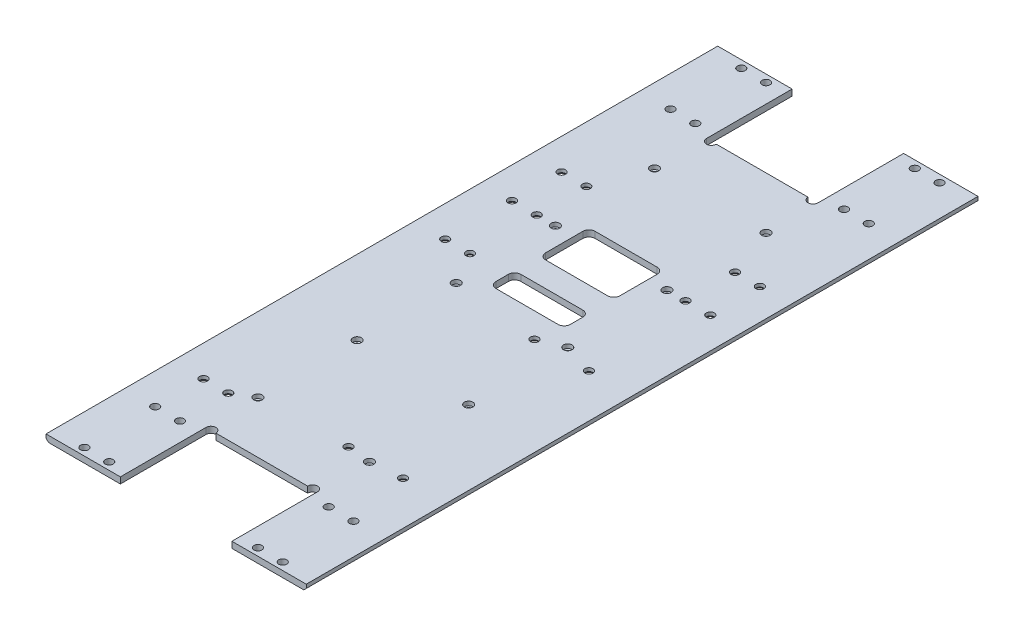
SolidWorks part; units mm, degrees
ref_plane "前视基准面" through (0, 0, 0) normal (0, 0, 1) x (1, 0, 0)
ref_plane "上视基准面" through (0, 0, 0) normal (0, 1, 0) x (1, 0, 0)
ref_plane "右视基准面" through (0, 0, 0) normal (1, 0, 0) x (0, 0, -1)
sketch "草图1" plane through (0, 0, 0) normal (0, 1, 0) x (1, 0, 0)
  line L6 (-52.5, -135.5) -> (52.5, -135.5)
  line L7 (52.5, -135.5) -> (52.5, 135.5)
  line L8 (-52.5, 135.5) -> (52.5, 135.5)
  line L9 (-52.5, -135.5) -> (-52.5, 135.5)
  point P8 (-50, 0)
extrude "凸台-拉伸1" add sketch "草图1" along normal blind 2.5
sketch "草图2" plane through (0, 2.5, 0) normal (0, 1, 0) x (1, 0, 0)
  circle A20 centre (13, -3.95) radius 1.6
  circle A21 centre (35, -3.95) radius 1.6
  circle A24 centre (35, -78.95) radius 1.6
  circle A25 centre (13, -78.95) radius 1.6
extrude "切除-拉伸1" cut sketch "草图2" against normal blind 10
chamfer "倒角4" distance 1 angle 45 2 edges at (52.5, 0, 0) (-52.5, 0, 0)
sketch "草图3" plane through (0, 0, 0) normal (0, -1, 0) x (1, 0, 0)
  line L0 (-22.5, 100.95) -> (22.5, 100.95)
  line L2 (-51.5, 135.5) -> (51.5, 135.5) construction
  line L3 (1.375, 0) -> (-1.375, 0) construction
  line L4 (22.5, 100.95) -> (22.5, 135.5)
  line L5 (22.5, 135.5) -> (-22.5, 135.5)
  line L6 (-22.5, 135.5) -> (-22.5, 100.95)
  line L7 (-22.5, -135.5) -> (-22.5, -100.95)
  line L8 (22.5, -135.5) -> (-22.5, -135.5)
  line L9 (22.5, -100.95) -> (22.5, -135.5)
  line L10 (-22.5, -100.95) -> (22.5, -100.95)
extrude "切除-拉伸2" cut sketch "草图3" against normal blind 10
sketch "草图4" plane through (0, 0, 0) normal (0, -1, 0) x (1, 0, 0)
  line L0 (0, -1.375) -> (0, 1.375) construction
  line L1 (22.5, -100.95) -> (-22.5, -100.95) construction
  line L2 (1.375, 0) -> (-1.375, 0) construction
  circle A0 centre (20.5, -100.95) radius 2
  circle A1 centre (-20.5, -100.95) radius 2
  circle A2 centre (-20.5, 100.95) radius 2
  circle A3 centre (20.5, 100.95) radius 2
extrude "切除-拉伸3" cut sketch "草图4" against normal blind 10
sketch "草图5" plane through (0, 2.5, 0) normal (0, 1, 0) x (1, 0, 0)
  line L0 (0, -1.375) -> (0, 1.375) construction
  line L3 (-1.375, 0) -> (1.375, 0) construction
  circle A0 centre (-40, 103.95) radius 1.6
  circle A1 centre (-30, 103.95) radius 1.6
  circle A4 centre (-40, 132.5) radius 1.6
  circle A5 centre (-30, 132.5) radius 1.6
  circle A6 centre (30, 132.5) radius 1.6
  circle A7 centre (40, 132.5) radius 1.6
  circle A8 centre (30, 103.95) radius 1.6
  circle A9 centre (40, 103.95) radius 1.6
  circle A10 centre (40, -103.95) radius 1.6
  circle A11 centre (30, -103.95) radius 1.6
  circle A12 centre (40, -132.5) radius 1.6
  circle A13 centre (30, -132.5) radius 1.6
  circle A14 centre (-30, -132.5) radius 1.6
  circle A15 centre (-40, -132.5) radius 1.6
  circle A16 centre (-30, -103.95) radius 1.6
  circle A17 centre (-40, -103.95) radius 1.6
extrude "切除-拉伸4" cut sketch "草图5" against normal blind 10
sketch "草图6" plane through (0, 2.5, 0) normal (0, 1, 0) x (1, 0, 0)
  line L0 (0, -1.375) -> (0, 1.375) construction
  circle A0 centre (40, 60) radius 1.6
  circle A1 centre (30, 60) radius 1.6
  circle A2 centre (40, 40) radius 1.6
  circle A3 centre (30, 40) radius 1.6
  circle A4 centre (-30, 40) radius 1.6
  circle A5 centre (-40, 40) radius 1.6
  circle A6 centre (-30, 60) radius 1.6
  circle A7 centre (-40, 60) radius 1.6
  circle A8 centre (-30, -84.45) radius 1.6
  circle A9 centre (-40, -84.45) radius 1.6
  circle A10 centre (-30, 13.05) radius 1.6
  circle A11 centre (-40, 13.05) radius 1.6
  dimension "D1" = 2
extrude "切除-拉伸5" cut sketch "草图6" against normal blind 10
sketch "草图7" plane through (0, 2.5, 0) normal (0, 1, 0) x (1, 0, 0)
  line L0 (0, -1.375) -> (0, 1.375) construction
  line L2 (-1.375, 0) -> (1.375, 0) construction
  circle A0 centre (-22.5, 0) radius 1.725
  circle A2 centre (-22.5, -40) radius 1.725
  circle A4 centre (-22.5, -80) radius 1.725
  circle A5 centre (-22.5, -20) radius 1.725 [skipped]
  circle A6 centre (-22.5, -60) radius 1.725 [skipped]
  circle A7 centre (22.5, -80) radius 1.725
  circle A8 centre (22.5, -40) radius 1.725
  circle A9 centre (22.5, 0) radius 1.725
  circle A10 centre (22.5, 40) radius 1.725
  circle A11 centre (22.5, 80) radius 1.725
  circle A12 centre (-22.5, 80) radius 1.725
  circle A13 centre (-22.5, 40) radius 1.725
  dimension "D1" = 5
extrude "切除-拉伸6" cut sketch "草图7" against normal blind 2
sketch "草图8" plane through (0, 2.5, 0) normal (0, 1, 0) x (1, 0, 0)
  line L0 (0, -1.375) -> (0, 1.375) construction
  circle A0 centre (-22.5, 80) radius 1.35
  circle A1 centre (-22.5, 40) radius 1.35
  circle A2 centre (-22.5, 0) radius 1.35
  circle A3 centre (-22.5, -40) radius 1.35
  circle A4 centre (-22.5, -80) radius 1.35
  circle A5 centre (22.5, -80) radius 1.35
  circle A6 centre (22.5, -40) radius 1.35
  circle A7 centre (22.5, 0) radius 1.35
  circle A8 centre (22.5, 40) radius 1.35
  circle A9 centre (22.5, 80) radius 1.35
  dimension "D1" = 5
extrude "切除-拉伸7" cut sketch "草图8" against normal up to next
chamfer "倒角5" distance 0.375 angle 45 10 edges at (22.5, 0.5, 78.275) (-22.5, 0.5, 81.725) (-22.5, 0.5, 41.725) (-22.5, 0.5, 1.725) (22.5, 0.5, 38.275) (22.5, 0.5, -1.725) (22.5, 0.5, -38.275) (-22.5, 0.5, -41.725) (-22.5, 0.5, -81.725) (22.5, 0.5, -78.275)
chamfer "倒角6" distance 1.15 angle 45 16 edges at (40, 0, -61.6) (30, 0, -61.6) (40, 0, -41.6) (30, 0, -41.6) (-30, 0, -61.6) (-40, 0, -61.6) (-30, 0, -41.6) (-40, 0, -41.6) (-30, 0, 82.85) (-40, 0, 82.85) (-30, 0, -14.65) (-40, 0, -14.65) (35, 0, 2.35) (13, 0, 2.35) (35, 0, 77.35) (13, 0, 77.35)
sketch "草图9" plane through (0, 0, 0) normal (0, -1, 0) x (1, 0, 0)
  line L0 (-15, -26.05) -> (-15, -46.05)
  line L1 (-15, -16.05) -> (15, -16.05)
  line L3 (15, -6.05) -> (-15, -6.05)
  line L4 (-15, -6.05) -> (-15, -16.05)
  line L5 (15, -6.05) -> (15, -16.05)
  line L6 (-15, -46.05) -> (15, -46.05)
  line L8 (15, -26.05) -> (-15, -26.05)
  line L11 (15, -46.05) -> (15, -26.05)
  line L13 (-15, -36.05) -> (15, -36.05) [skipped]
  line L14 (-15, -26.05) -> (-15, -36.05) [skipped]
  line L15 (15, -26.05) -> (15, -36.05) [skipped]
  dimension "D1" = 2
extrude "切除-拉伸8" cut sketch "草图9" against normal blind 12 contours L5 L3 L4 L1 | L11 L8 L0 L6 region at (0, 0, -11.05)
fillet "圆角1" radius 2.5 8 edges at (15, 1.25, -16.05) (15, 1.25, -6.05) (-15, 1.25, -16.05) (-15, 1.25, -6.05) (-15, 1.25, -46.05) (15, 1.25, -46.05) (15, 1.25, -26.05) (-15, 1.25, -26.05)
